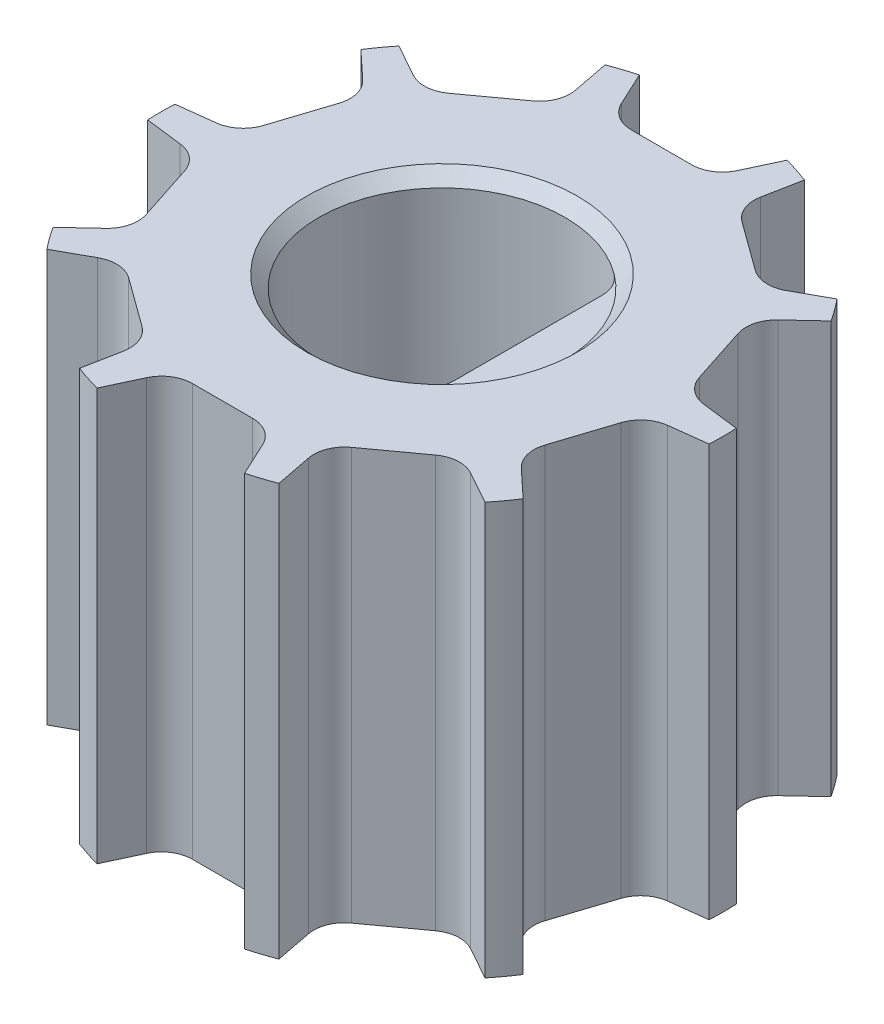
SolidWorks part; units mm, degrees
material "6061-T6 (SS)"
ref_plane "Ebene vorne" through (0, 0, 0) normal (0, 0, 1) x (1, 0, 0)
ref_plane "Ebene oben" through (0, 0, 0) normal (0, 1, 0) x (1, 0, 0)
ref_plane "Ebene rechts" through (0, 0, 0) normal (1, 0, 0) x (0, 0, -1)
ref_axis "Achse1" through (0, -12.75, 0) along (0, 1, 0)
sketch "Skizze1" plane through (0, 0, 0) normal (0, 1, 0) x (1, 0, 0)
  circle A0 centre (0, 0) radius 4.57
  circle A1 centre (0, 0) radius 2
  dimension "D1" = 9.14
  dimension "D2" = 4
extrude "Aufsatz-Linear austragen1" add sketch "Skizze1" along normal blind 6.7
sketch "Skizze12" plane through (0, 6.7, 0) normal (0, 1, 0) x (1, 0, 0)
  line L0 (0, 9.2022) -> (0, -8.7185) construction
  line L1 (-8.4713, 0) -> (7.9602, 0) construction
  line L2 (-1.2, 4.4096) -> (-0.8085, 3.57)
  line L3 (1.2, 4.4096) -> (0.8085, 3.57)
  line L4 (-2.8195, 3.57) -> (2.5735, 3.57) construction
  line L5 (-2.9704, 4.57) -> (2.868, 4.57) construction
  line L6 (-0.8085, 3.57) -> (0.8085, 3.57)
  circle A1 centre (0, 0) radius 4.57 construction
  circle A2 centre (0, 0) radius 4.57 construction
  arc A4 (-1.2, 4.4096) -> (1.2, 4.4096) centre (0, 0) cw
  dimension "D1" = 1
  dimension "D5" = 1.6169
  dimension "D6" = 9.14
  dimension "D2" = 2.4
  dimension "D3" = 50
  dimension "D4" = 3.57
extrude "Schnitt-Linear austragen1" cut sketch "Skizze12" against normal through all
fillet "Verrundung1" radius 0.5 2 edges at (0.8085, 3.35, -3.57) (-0.8085, 3.35, -3.57)
pattern_circular "Kreismuster1" count 10 over 360 about axis through (0, -12.75, 0) along (0, 1, 0) of "Schnitt-Linear austragen1", "Verrundung1"
chamfer "Fase2" distance 0.2 angle 45 2 edges at (0, 6.7, 2) (0, 0, 2)
ref_plane "Plane1" through (0, 3.35, 0) normal (0, -1, 0) x (-1, 0, 0)
sketch "Sketch1" plane through (0, 3.35, 0) normal (0, -1, 0) x (-1, 0, 0)
  line L0 (0, 0) -> (0, -5.2371) construction
  line L1 (0, -5.2371) -> (0, 5.3993) construction
  line L2 (-1.4, -5.2371) -> (-1.4, 5.3993) construction
  line L3 (-1.4, 1.4283) -> (-1.4, -1.4283)
  circle A0 centre (0, 0) radius 2 construction
  circle A1 centre (0, 0) radius 2 construction
  arc A2 (-1.4, 1.4283) -> (-1.4, -1.4283) centre (0, 0) ccw
  dimension "D1" = 1.4
ref_plane "Plane2" through (0, 6.5, 0) normal (0, -1, 0) x (-1, 0, 0)
ref_plane "Plane3" through (0, 0.2, 0) normal (0, 1, 0) x (1, 0, 0)
extrude "Boss-Extrude1" add sketch "Sketch1" against normal up to surface (3.15 mm away) and the other way up to surface (3.15 mm away) up to plane "Plane2" other way up to plane "Plane3"
fillet "Fillet1" radius 0.5 2 edges at (1.4, 3.35, -1.4283) (1.4, 3.35, 1.4283)
